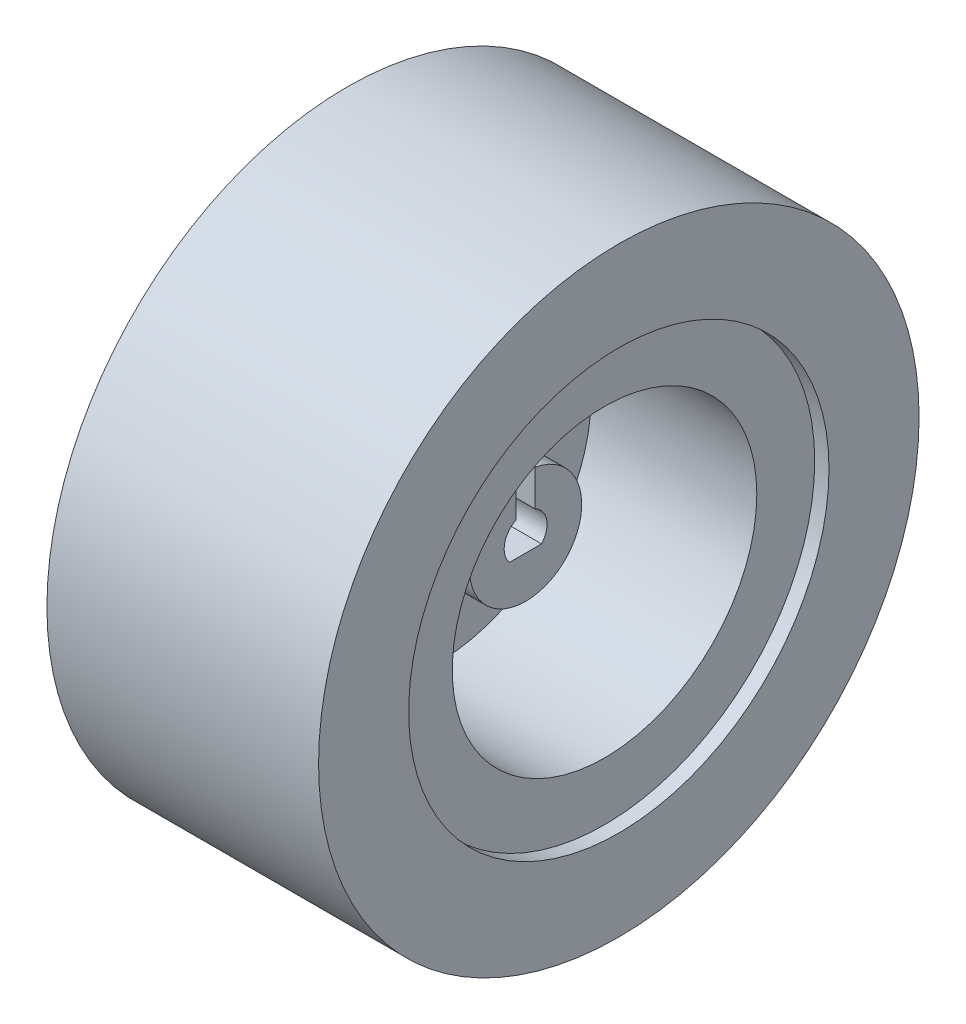
SolidWorks part; units mm, degrees
ref_plane "Front Plane" through (0, 0, 0) normal (0, 0, 1) x (1, 0, 0)
ref_plane "Top Plane" through (0, 0, 0) normal (0, 1, 0) x (1, 0, 0)
ref_plane "Right Plane" through (0, 0, 0) normal (1, 0, 0) x (0, 0, -1)
sketch "Sketch1" plane through (0, 0, 0) normal (1, 0, 0) x (0, 0, -1)
  circle A0 centre (0, 0) radius 21
  dimension "D1" = 42
extrude "Boss-Extrude1" add sketch "Sketch1" along normal blind 9.5 and the other way blind 9.5
sketch "Sketch5" plane through (9.5, 0, 0) normal (1, 0, 0) x (0, 0, -1)
  circle A0 centre (0, 0) radius 14.7
  dimension "D1" = 29.4
extrude "Cut-Extrude3" cut sketch "Sketch5" against normal blind 1
sketch "Sketch6" plane through (8.5, 0, 0) normal (1, 0, 0) x (0, 0, -1)
  circle A0 centre (0, 0) radius 10.65
  dimension "D1" = 21.3
extrude "Cut-Extrude4" cut sketch "Sketch6" against normal blind 11.6
sketch "Sketch7" plane through (-3.1, 0, 0) normal (1, 0, 0) x (0, 0, -1)
  circle A0 centre (0, 0) radius 3.925
  dimension "D1" = 7.85
extrude "Boss-Extrude2" add sketch "Sketch7" along normal blind 6.08
sketch "Sketch2" plane through (9.5, 0, 0) normal (1, 0, 0) x (0, 0, -1)
  line L0 (-1.9974, 0) -> (-0.665, 0) construction
  line L1 (-1.118, -1) -> (1.118, -1)
  line L2 (-0.665, 8.8797) -> (-0.665, 1.3445)
  line L3 (-0.665, 8.8797) -> (0.665, 8.8797)
  line L5 (0.665, 8.8797) -> (0.665, 1.3445)
  line L6 (-0.665, 8.8797) -> (0.4507, 1.4307) construction
  line L7 (-0.4507, 1.4307) -> (0.665, 8.8797) construction
  line L8 (0.665, 0) -> (2.227, 0) construction
  arc A0 (1.118, -1) -> (0.665, 1.3445) centre (0, 0) ccw
  arc A1 (-0.665, 1.3445) -> (-1.118, -1) centre (0, 0) ccw
  point P5 (0, 4.4399)
  dimension "D1" = 3
  dimension "D2" = 1
  dimension "D3" = 8.8797
  dimension "D4" = 1.33
extrude "Cut-Extrude1" cut sketch "Sketch2" against normal through all
sketch "Sketch4" plane through (-9.5, 0, 0) normal (-1, 0, 0) x (0, 0, 1)
  circle A0 centre (0, 0) radius 14.7
  dimension "D1" = 29.4
extrude "Cut-Extrude2" cut sketch "Sketch4" against normal blind 4.5
equation "\"wheel diam\" = 42mm"
equation "\"wheel_hole\"= 3.0"
equation "\"wheel_depth\" = 19mm"
equation "\"D1@Sketch1\"= \"wheel diam\""
equation "\"D1@Sketch2\"= \"wheel_hole\""
